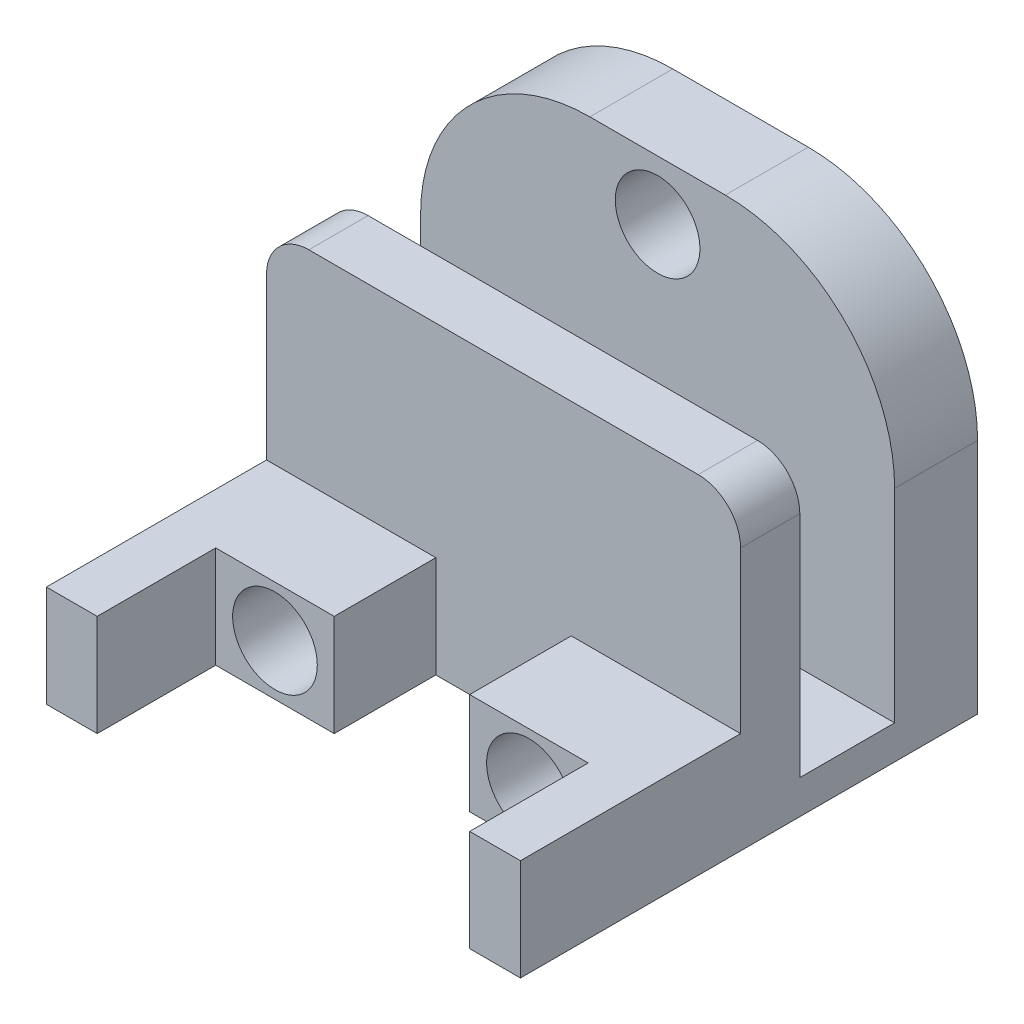
SolidWorks part; units mm, degrees
ref_plane "Front" through (0, 0, 0) normal (0, 0, 1) x (1, 0, 0)
ref_plane "Top" through (0, 0, 0) normal (0, 1, 0) x (1, 0, 0)
ref_plane "Right" through (0, 0, 0) normal (1, 0, 0) x (0, 0, -1)
sketch "Sketch1" plane through (0, 0, 0) normal (0, 1, 0) x (1, 0, 0)
  line L0 (0, 0) -> (0, 25.4)
  line L1 (0, 25.4) -> (35.56, 25.4)
  line L2 (35.56, 25.4) -> (35.56, 0)
  line L3 (31.75, 0) -> (22.86, 0)
  line L4 (22.86, 0) -> (22.86, 7.62)
  line L6 (12.7, 7.62) -> (12.7, 0)
  line L7 (12.7, 0) -> (3.81, 0)
  line L8 (3.81, 0) -> (3.81, -8.89)
  line L9 (3.81, -8.89) -> (0, -8.89)
  line L10 (0, -8.89) -> (0, 0)
  line L11 (0, 0) -> (0, -8.89)
  line L12 (31.75, 0) -> (31.75, -8.89)
  line L13 (31.75, -8.89) -> (35.56, -8.89)
  line L14 (35.56, -8.89) -> (35.56, 0)
  line L15 (12.7, 7.62) -> (22.86, 7.62)
  point P14 (22.86, 7.9257)
  dimension "D1" = 8.89
  dimension "D2" = 7.62
  dimension "D3" = 25.4
  dimension "D4" = 10.16
  dimension "D5" = 35.56
extrude "Boss-Extrude1" add sketch "Sketch1" along normal blind 7.62 contours L6 L15 L4 L3 L12 L13 L14 L2 L1 L0 L10 L9 L8 L7 region at (17.78, 0, -12.1705)
sketch "Sketch2" plane through (0, 7.62, 0) normal (0, 1, 0) x (1, 0, 0)
  line L0 (0, 7.62) -> (35.56, 7.62)
  line L2 (35.56, -8.89) -> (35.56, 25.4) construction
  line L3 (0, -8.89) -> (0, 25.4) construction
  line L4 (0, 25.4) -> (35.56, 25.4) construction
  line L5 (0, 7.62) -> (0, 25.4)
  line L6 (35.56, 7.62) -> (35.56, 25.4)
  line L7 (0, 25.4) -> (35.56, 25.4)
  line L8 (12.7, 7.62) -> (22.86, 7.62) construction
  point P3 (17.78, 7.62)
  point P7 (17.78, 10.3616)
extrude "Boss-Extrude2" add sketch "Sketch2" along normal blind 22.86
sketch "Sketch4" plane through (0, 30.48, 0) normal (0, 1, 0) x (1, 0, 0)
  line L0 (0, 19.177) -> (35.56, 19.177)
  line L1 (0, 25.4) -> (0, 7.62) construction
  line L2 (35.56, 7.62) -> (35.56, 25.4) construction
  line L3 (0, 12.065) -> (35.56, 12.065)
  line L4 (0, 19.177) -> (0, 12.065)
  line L5 (35.56, 19.177) -> (35.56, 12.065)
  line L6 (0, 7.62) -> (35.56, 7.62) construction
  dimension "D1" = 7.112
  dimension "D2" = 4.445
extrude "Cut-Extrude2" cut sketch "Sketch4" against normal blind 27.94
sketch "Sketch5" plane through (0, 30.48, 0) normal (0, 1, 0) x (1, 0, 0)
  line L0 (35.56, 7.62) -> (35.56, 12.065) construction
  line L1 (0, 7.62) -> (35.56, 7.62) construction
  line L2 (0, 12.065) -> (0, 7.62) construction
  line L3 (0, 12.065) -> (35.56, 12.065) construction
  line L4 (35.56, 7.62) -> (35.56, 12.065)
  line L5 (0, 7.62) -> (35.56, 7.62)
  line L6 (0, 12.065) -> (0, 7.62)
  line L7 (0, 12.065) -> (35.56, 12.065)
extrude "Cut-Extrude3" cut sketch "Sketch5" against normal blind 7.62
sketch "Sketch6" plane through (0, 0, -25.4) normal (0, 0, -1) x (-1, 0, 0)
  line L0 (-17.78, 30.48) -> (-17.78, 20.6523) construction
  line L1 (-35.56, 30.48) -> (0, 30.48) construction
  circle A0 centre (-17.78, 26.035) radius 3.175
  point P2 (0, 0)
  point P7 (-17.78, 25.8077)
  dimension "D1" = 6.35
  dimension "D2" = 4.445
extrude "Cut-Extrude4" cut sketch "Sketch6" against normal blind 6.35
sketch "Sketch7" plane through (0, 0, 0) normal (0, 0, 1) x (1, 0, 0)
  line L0 (27.305, 7.62) -> (27.305, 3.81) construction
  line L1 (31.75, 7.62) -> (22.86, 7.62) construction
  line L2 (27.305, 3.81) -> (22.86, 3.81) construction
  line L3 (22.86, 7.62) -> (22.86, 0) construction
  line L4 (17.78, 0) -> (17.78, 9.9153) construction
  line L5 (12.7, 0) -> (22.86, 0) construction
  line L6 (8.255, 3.81) -> (12.7, 3.81) construction
  line L7 (8.255, 7.62) -> (8.255, 3.81) construction
  circle A0 centre (27.305, 3.81) radius 3.175
  circle A1 centre (8.255, 3.81) radius 3.175
  dimension "D1" = 6.35
extrude "Cut-Extrude5" cut sketch "Sketch7" against normal blind 9.525
fillet "Fillet1" radius 12.7 2 edges at (0, 30.48, -22.2885) (35.56, 30.48, -22.2885)
fillet "Fillet2" radius 3.175 2 edges at (0, 22.86, -9.8425) (35.56, 22.86, -9.8425)
